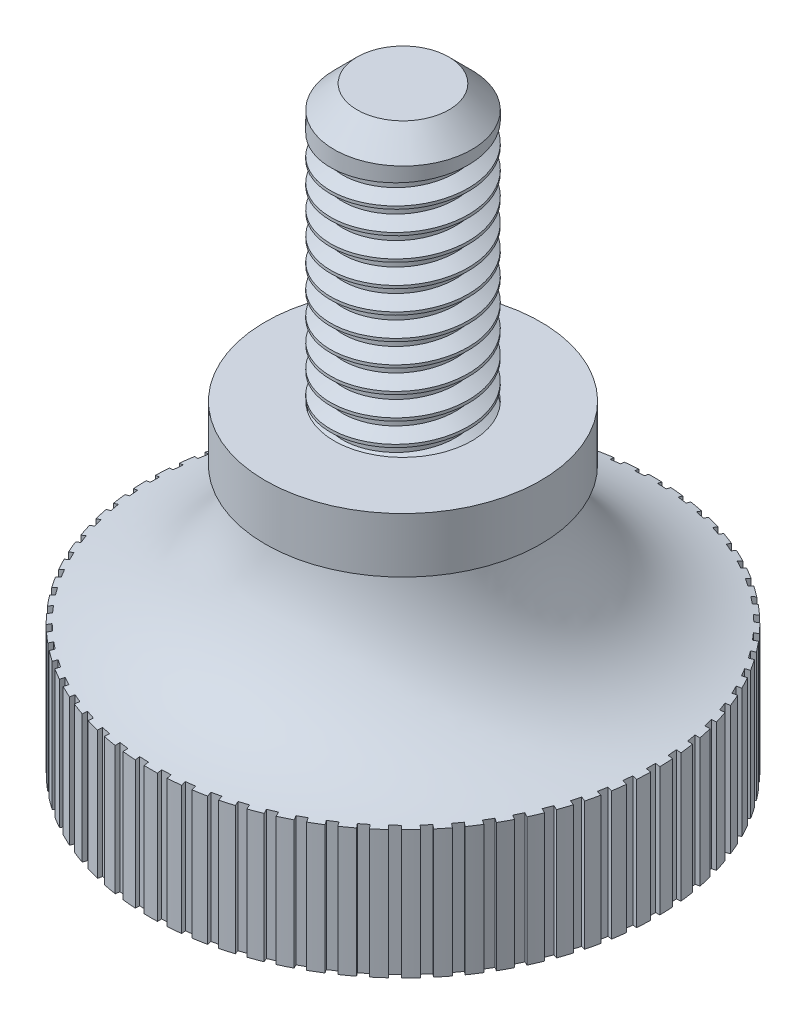
SolidWorks part; units mm, degrees
ref_plane "前视基准面" through (0, 0, 0) normal (0, 0, 1) x (1, 0, 0)
ref_plane "上视基准面" through (0, 0, 0) normal (0, 1, 0) x (1, 0, 0)
ref_plane "右视基准面" through (0, 0, 0) normal (1, 0, 0) x (0, 0, -1)
sketch "草图1" plane through (0, 0, 0) normal (0, 1, 0) x (1, 0, 0)
  circle A0 centre (0, 0) radius 5.5
  dimension "D1" = 11
extrude "凸台-拉伸1" add sketch "草图1" along normal blind 2.8
ref_plane "基准面1" through (0, 5.8, 0) normal (0, 1, 0) x (1, 0, 0)
sketch "草图2" plane through (0, 5.8, 0) normal (0, 1, 0) x (1, 0, 0)
  circle A0 centre (0, 0) radius 2.6
  dimension "D1" = 5.2
sketch "草图3" plane through (0, 0, 0) normal (0, 0, 1) x (1, 0, 0)
  line L0 (2.6, 5.8) -> (-2.6, 5.8) construction
  line L1 (-2.6, 5.8) -> (0, 5.8)
  line L2 (0, 5.8) -> (0, 2.8)
  line L3 (5.5, 2.8) -> (-5.5, 2.8) construction
  line L4 (0, 2.8) -> (-5.5, 2.8)
  spline S0 degree 2 poles (-5.5, 2.8) (-2.988, 3.2585) (-2.6, 5.8) knots 0 0 0 1 1 1
revolve "旋转1" add sketch "草图3" angle 360 about L2
sketch "草图4" plane through (0, 5.8, 0) normal (0, 1, 0) x (1, 0, 0)
  circle A0 centre (0, 0) radius 3
  dimension "D1" = 6
extrude "凸台-拉伸2" add sketch "草图4" along normal blind 1.2
sketch "草图5" plane through (0, 7, 0) normal (0, 1, 0) x (1, 0, 0)
  circle A0 centre (0, 0) radius 1.5
  dimension "D1" = 3
extrude "凸台-拉伸3" add sketch "草图5" along normal blind 6
chamfer "倒角1" distance 0.5 angle 45 1 edges at (0, 13, 1.5)
thread "螺纹线1" pitch 0.5 method cut profile "螺纹线轮廓1" start angle 0, offset 0, length 6, pitch 0.5, diameter 3
ref_plane "基准面2" through (-1.5, 12.5, 0) normal (0, 0, 1) x (-1, 0, 0)
sketch "螺纹线轮廓1" plane through (-1.5, 12.5, 0) normal (0, 0, 1) x (-1, 0, 0)
  line L0 (0, 0) -> (0, 0.5) construction
  line L11 (0, 0) -> (0, 0.4375)
  line L12 (0, 0.4375) -> (-0.2706, 0.2812)
  line L13 (-0.2706, 0.2812) -> (-0.2706, 0.1562)
  line L15 (-0.2706, 0.1562) -> (0, 0)
  line L17 (-0.2706, 0.2187) -> (0, 0.2187) construction
  point P2 (0, 0)
  dimension "Pitch" = 0.5
  dimension "Profile_Angle" = 60
  dimension "Profile_Land" = 0.125
  dimension "Profile_Height" = 0.2706
sketch "草图6" plane through (0, 0, 0) normal (0, -1, 0) x (-1, 0, 0)
  line L0 (0, 0) -> (5.4068, 0) construction
  line L1 (6.0341, -0.1) -> (5.4068, -0.1)
  line L2 (6.0341, -0.1) -> (6.0341, 0.1)
  line L3 (6.0341, 0.1) -> (5.4068, 0.1)
  line L4 (5.4068, -0.1) -> (5.4068, 0.1)
  dimension "D1" = 0.2
ref_axis "基准轴1" through (0, 7, 0) along (0, -1, 0)
extrude "切除-拉伸1" cut sketch "草图6" against normal blind 10
pattern_circular "阵列(圆周)1" count 70 over 360 about axis through (0, 7, 0) along (0, -1, 0) of "切除-拉伸1"
